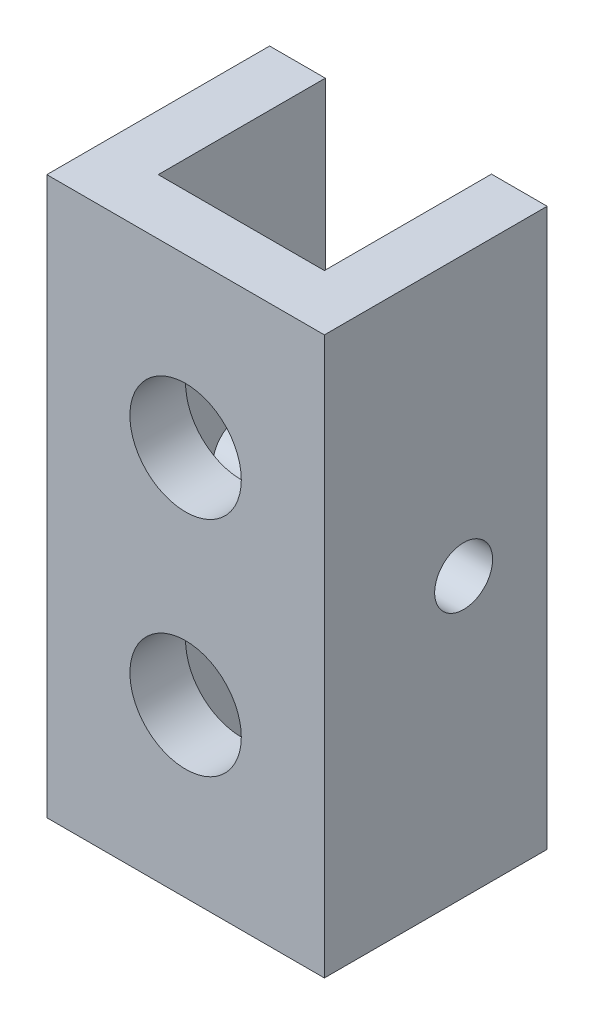
SolidWorks part; units mm, degrees
ref_plane "Front Plane" through (0, 0, 0) normal (0, 0, 1) x (1, 0, 0)
ref_plane "Top Plane" through (0, 0, 0) normal (0, 1, 0) x (1, 0, 0)
ref_plane "Right Plane" through (0, 0, 0) normal (1, 0, 0) x (0, 0, -1)
sketch "Sketch1" plane through (0, 0, 0) normal (0, 1, 0) x (1, 0, 0)
  line L0 (0, 0) -> (0, 25.4)
  line L1 (0, 25.4) -> (6.35, 25.4)
  line L2 (6.35, 25.4) -> (6.35, 6.35)
  line L3 (6.35, 6.35) -> (25.2944, 6.35)
  line L7 (31.6444, 0) -> (0, 0)
  line L8 (15.8222, 0) -> (15.8222, 6.35) construction
  line L9 (31.6444, 25.4) -> (25.2944, 25.4)
  line L10 (25.2944, 25.4) -> (25.2944, 6.35)
  line L11 (31.6444, 0) -> (31.6444, 25.4)
  dimension "D1" = 6.35
  dimension "D2" = 6.35
  dimension "D3" = 25.4
extrude "Boss-Extrude1" add sketch "Sketch1" along normal blind 63.5
sketch "Sketch2" plane through (0, 0, 0) normal (0, 0, 1) x (1, 0, 0)
  line L0 (15.8222, 63.5) -> (15.8222, 0) construction
  line L1 (0, 63.5) -> (31.6444, 63.5) construction
  line L2 (0, 0) -> (31.6444, 0) construction
  circle A0 centre (15.8222, 44.45) radius 6.35
  circle A1 centre (15.8222, 19.05) radius 6.35
  point P8 (15.8222, 31.75)
  dimension "D1" = 25.4
  dimension "D2" = 12.7
extrude "Cut-Extrude1" cut sketch "Sketch2" against normal through all
sketch "Sketch5" plane through (6.35, 0, 0) normal (1, 0, 0) x (0, 0, -1)
  line L0 (6.35, 31.75) -> (25.4, 31.75) construction
  line L1 (6.35, 63.5) -> (6.35, 0) construction
  line L2 (25.4, 63.5) -> (25.4, 0) construction
  line L3 (15.875, 63.5) -> (15.875, 0) construction
  line L4 (6.35, 63.5) -> (25.4, 63.5) construction
  line L5 (6.35, 0) -> (25.4, 0) construction
  circle A0 centre (15.875, 31.75) radius 3.302
extrude "Cut-Extrude2" cut sketch "Sketch5" against normal through all and the other way through all
